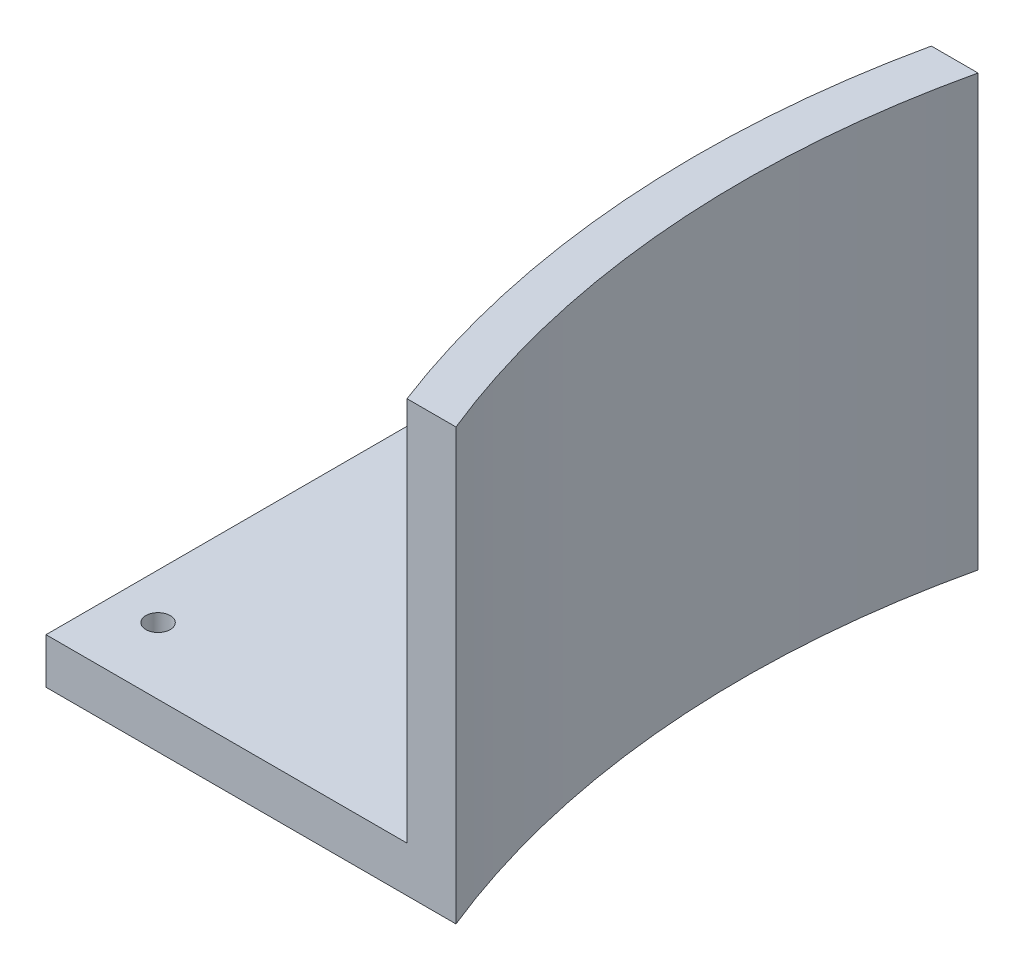
SolidWorks part; units mm, degrees
ref_plane "Front Plane" through (0, 0, 0) normal (0, 0, 1) x (1, 0, 0)
ref_plane "Top Plane" through (0, 0, 0) normal (0, 1, 0) x (1, 0, 0)
ref_plane "Right Plane" through (0, 0, 0) normal (1, 0, 0) x (0, 0, -1)
sketch "Sketch1" plane through (0, 0, 0) normal (0, 1, 0) x (1, 0, 0)
  line L0 (50.8, 79.121) -> (0, 79.121)
  line L1 (0, 79.121) -> (0, 0)
  line L2 (0, 0) -> (57.15, 0)
  arc A1 (50.8, 79.121) -> (57.15, 0) centre (179.5475, 49.6385) ccw
  dimension "D2" = 264.16
  dimension "D3" = 79.121
  dimension "D4" = 57.15
extrude "Boss-Extrude1" add sketch "Sketch1" along normal blind 60
sketch "Sketch3" plane through (0, 0, 0) normal (0, 1, 0) x (1, 0, 0)
  line L0 (51.2655, -2.3865) -> (0, 0)
  line L2 (0, 0) -> (0, 79.121)
  line L3 (0, 79.121) -> (44.2935, 79.121)
  line L5 (50.8, 79.121) -> (0, 79.121) construction
  arc A3 (44.6102, 80.5384) -> (51.2655, -2.3865) centre (179.5475, 49.6385) ccw
  arc A4 (44.2935, 79.121) -> (51.2655, -2.3865) centre (179.5475, 49.6385) ccw
  dimension "D1" = 6.35
extrude "Cut-Extrude1" cut sketch "Sketch3" against normal offset from surface (53.65 mm away) 6.35 from surface up to face at (25.4665, 0, -39.4384) starting at face at (25.4665, 60, -39.4384)
sketch "Sketch4" plane through (0, 6.35, 0) normal (0, 1, 0) x (1, 0, 0)
  line L0 (44.2935, 79.121) -> (0, 79.121) construction
  line L1 (0, 79.121) -> (0, 0) construction
  circle A0 centre (6.35, 72.771) radius 1.7
  circle A1 centre (25.4, 72.771) radius 1.7
  circle A3 centre (6.35, 9.271) radius 1.7
  circle A4 centre (25.4, 9.271) radius 1.7 [skipped]
  dimension "D1" = 3.4
  dimension "D2" = 6.35
  dimension "D3" = 6.35
  dimension "D5" = 2
extrude "Cut-Extrude2" cut sketch "Sketch4" against normal through all
equation "\"tightTol\"= 0.005in"
equation "\"normTol\"= 0.01in"
equation "\"looseTol\"= 0.02in"
equation "\"D3@Sketch1\"=3.125000in-\"normTol\""
equation "\"D1@Sketch4\"=3.4mm"
equation "\"D1@Boss-Extrude1\"=60mm"
